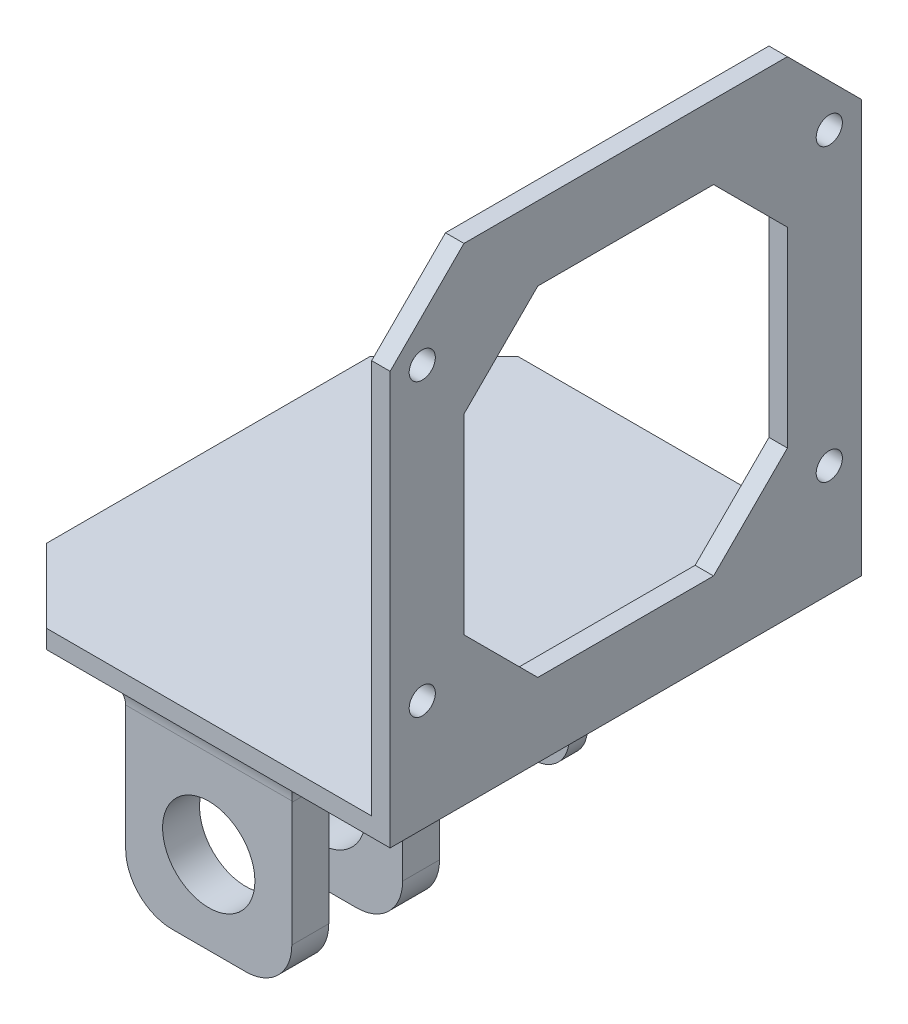
SolidWorks part; units mm, degrees
material "ABS PC"
ref_plane "Front Plane" through (0, 0, 0) normal (0, 0, 1) x (1, 0, 0)
ref_plane "Top Plane" through (0, 0, 0) normal (0, 1, 0) x (1, 0, 0)
ref_plane "Right Plane" through (0, 0, 0) normal (1, 0, 0) x (0, 0, -1)
sketch "Sketch1" plane through (0, 0, 0) normal (0, 1, 0) x (1, 0, 0)
  line L0 (0, 40.513) -> (71.755, 40.513) construction
  line L1 (0, 0) -> (71.755, 0)
  line L2 (0, 0) -> (0, 81.026)
  line L3 (0, 81.026) -> (71.755, 81.026)
  line L4 (71.755, 0) -> (71.755, 81.026)
  line L5 (35.8775, 81.026) -> (35.8775, 0) construction
  dimension "D1" = 71.755
  dimension "D2" = 81.026
extrude "Boss-Extrude1" add sketch "Sketch1" along normal blind 3.175
ref_plane "Plane2" through (0, 0, -40.513) normal (0, 0, -1) x (-1, 0, 0)
ref_plane "Plane1" through (35.8775, 0, 0) normal (1, 0, 0) x (0, 0, -1)
sketch "Sketch3" plane through (0, 3.175, 0) normal (0, 1, 0) x (1, 0, 0)
  line L0 (71.755, 0) -> (68.58, 0)
  line L1 (0, 0) -> (71.755, 0) construction
  line L2 (68.58, 0) -> (68.58, 81.026)
  line L3 (71.755, 81.026) -> (0, 81.026) construction
  line L4 (68.58, 81.026) -> (71.755, 81.026)
  line L5 (71.755, 81.026) -> (71.755, 0)
  dimension "D1" = 3.175
extrude "Boss-Extrude4" add sketch "Sketch3" along normal blind 80.518
sketch "Sketch8" plane through (0, 0, -40.513) normal (0, 0, 1) x (1, 0, 0)
  line L0 (26.3525, 0) -> (26.3525, -31.75)
  line L1 (0, 0) -> (71.755, 0) construction
  line L2 (45.4025, 0) -> (45.4025, -31.75)
  line L3 (45.4025, -31.75) -> (26.3525, -31.75)
  line L4 (26.3525, 0) -> (45.4025, 0)
  line L5 (35.8775, -1.7463) -> (35.8775, 1.7463) construction
  circle A1 centre (35.8775, -21.25) radius 3.175
  point P8 (35.8775, 0)
  dimension "D3" = 10.5
  dimension "D4" = 6.35
  dimension "D1" = 19.05
  dimension "D2" = 31.75
extrude "Boss-Extrude10" add sketch "Sketch8" along normal blind 3.175 from offset 19.812 contours L4 L2 L3 L0 | A1 offset against normal yes
sketch "Sketch13" plane through (71.755, 0, 0) normal (1, 0, 0) x (0, 0, -1)
  circle A0 centre (75.526, 69.175) radius 2.25
  circle A1 centre (5.526, 69.175) radius 2.25
  circle A2 centre (5.526, 19.175) radius 2.25
  circle A3 centre (75.526, 19.175) radius 2.25
  dimension "D1" = 4.5
extrude "Cut-Extrude2" cut sketch "Sketch13" against normal up to next
sketch "Sketch9" plane through (71.755, 0, 0) normal (1, 0, 0) x (0, 0, -1)
  line L0 (0, 83.693) -> (81.026, 0) construction
  line L1 (81.026, 83.693) -> (81.026, 0) construction
  line L2 (12.7, 12.7) -> (68.326, 12.7)
  line L3 (12.7, 12.7) -> (12.7, 70.993)
  line L4 (12.7, 70.993) -> (68.326, 70.993)
  line L5 (68.326, 12.7) -> (68.326, 70.993)
  line L6 (12.7, 12.7) -> (68.326, 70.993) construction
  line L7 (12.7, 70.993) -> (68.326, 12.7) construction
  line L8 (0, 83.693) -> (81.026, 83.693) construction
  point P3 (0, 0)
  point P4 (40.513, 41.8465)
  dimension "D1" = 12.7
  dimension "D2" = 12.7
extrude "Cut-Extrude1" cut sketch "Sketch9" against normal up to next contours L3 L2 L5 L4
fillet "Fillet3" radius 12.7 4 edges at (70.1675, 83.693, 0) (0, 1.5875, 0) (70.1675, 83.693, -81.026) (0, 1.5875, -81.026) profile chamfer
chamfer "Chamfer1" distance 12.7 angle 45 4 edges at (70.1675, 12.7, -12.7) (70.1675, 12.7, -68.326) (70.1675, 70.993, -68.326) (70.1675, 70.993, -12.7)
sketch "Sketch10" plane through (0, 0, 0) normal (0, 0, 1) x (1, 0, 0)
  line L0 (35.8775, -21.25) -> (35.8775, 0)
  line L2 (21.59, 0) -> (21.59, -35.5375)
  line L3 (12.7, 0) -> (71.755, 0) construction
  line L4 (21.59, -35.5375) -> (50.165, -35.5375)
  line L5 (50.165, -35.5375) -> (50.165, 0)
  line L6 (21.59, 0) -> (50.165, 0)
  circle A0 centre (35.8775, -21.25) radius 7.9375
  line M10 (12.7, 0) -> (71.755, 0)
  dimension "D1" = 15.875
  dimension "D2" = 14.2875
  dimension "D3" = 28.575
  dimension "D4" = 14.2875
extrude "Boss-Extrude11" add sketch "Sketch10" along normal blind 6.35 from offset 11.0376 contours A0 L2 L4 L5 M10 region at (43.0212, -0.456, 0) offset against normal yes
pattern_linear "LPattern1" count 2 spacing 19.05 along (0, 0, -1) of "Boss-Extrude11"
fillet "Fillet1" radius 6.35 2 edges at (45.4025, -31.75, -58.7375) (26.3525, -31.75, -58.7375)
fillet "Fillet2" radius 8.4667 4 edges at (45.4025, 0, -58.7375) (35.8775, 0, -57.15) (26.3525, 0, -58.7375) (35.8775, 0, -60.325)
fillet "Fillet4" radius 6.35 8 edges at (50.165, 0, -26.9126) (50.165, 0, -7.8626) (35.8775, 0, -4.6876) (21.59, 0, -7.8626) (35.8775, 0, -11.0376) (35.8775, 0, -23.7376) (21.59, 0, -26.9126) (35.8775, 0, -30.0876)
fillet "Fillet5" radius 7.9375 4 edges at (50.165, -35.5375, -26.9126) (50.165, -35.5375, -7.8626) (21.59, -35.5375, -7.8626) (21.59, -35.5375, -26.9126)
